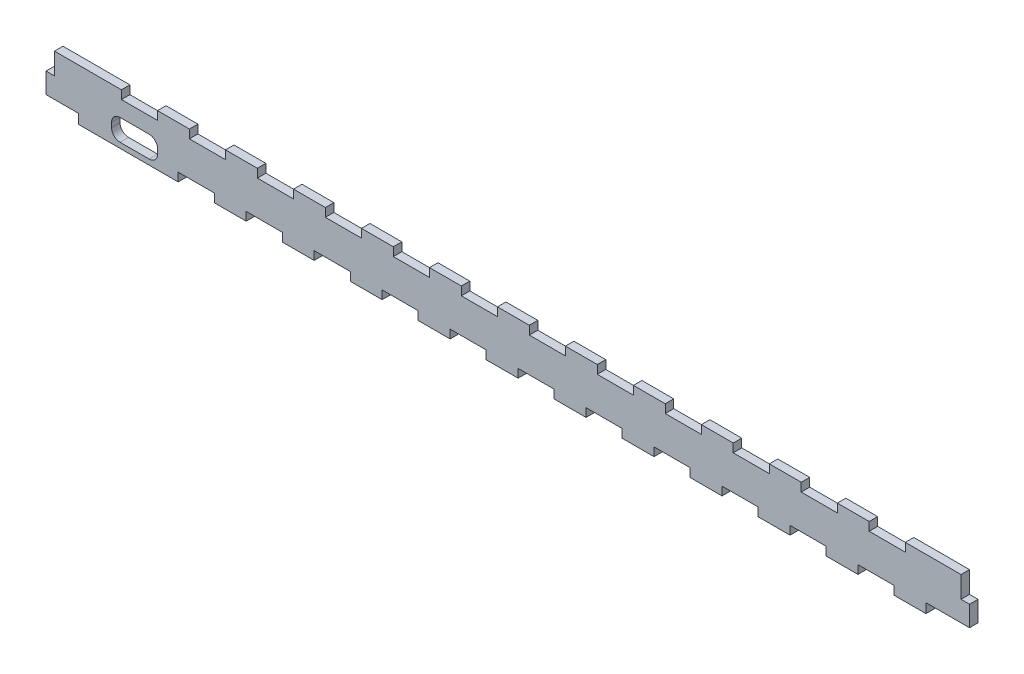
SolidWorks part; units mm, degrees
ref_plane "Plan de face" through (0, 0, 0) normal (0, 0, 1) x (1, 0, 0)
ref_plane "Plan de dessus" through (0, 0, 0) normal (0, 1, 0) x (1, 0, 0)
ref_plane "Plan de droite" through (0, 0, 0) normal (1, 0, 0) x (0, 0, -1)
sketch "Esquisse1" plane through (0, 0, 0) normal (0, 0, 1) x (1, 0, 0)
  line L1 (-108.68, -6.055) -> (108.68, -6.055)
  line L2 (-108.68, -6.055) -> (-108.68, 6.055)
  line L3 (-108.68, 6.055) -> (108.68, 6.055)
  line L4 (108.68, -6.055) -> (108.68, 6.055)
  line L5 (-108.68, -6.055) -> (108.68, 6.055) construction
  line L6 (-108.68, 6.055) -> (108.68, -6.055) construction
  point P0 (0, 0)
extrude "Boss.-Extru.1" add sketch "Esquisse1" along normal blind 2
sketch "Esquisse2" plane through (0, 0, 2) normal (0, 0, 1) x (1, 0, 0)
  line L1 (-109.57, -4.055) -> (-108.68, -4.055)
  line L2 (-109.57, -4.055) -> (-109.57, -6.055)
  line L3 (-109.57, -6.055) -> (-101.07, -6.055)
  line L4 (-101.07, -4.055) -> (-101.07, -6.055)
  line L5 (-90.93, 4.055) -> (-82.43, 4.055)
  line L6 (-90.93, 4.055) -> (-90.93, 6.055)
  line L7 (-90.93, 6.055) -> (-82.43, 6.055)
  line L8 (-82.43, 4.055) -> (-82.43, 6.055)
  line L9 (-108.68, -4.055) -> (-101.32, -4.055) construction
  line L10 (-101.32, -6.055) -> (-108.68, -6.055) construction
  line L12 (-90.68, 4.055) -> (-82.68, 4.055) construction
  line L13 (-90.68, 6.055) -> (-82.68, 6.055) construction
  line L22 (-77.57, -4.055) -> (-69.07, -4.055)
  line L23 (-77.57, -4.055) -> (-77.57, -6.055)
  line L24 (-77.57, -6.055) -> (-69.07, -6.055)
  line L25 (-69.07, -4.055) -> (-69.07, -6.055)
  line L30 (-61.57, -4.055) -> (-53.07, -4.055)
  line L31 (-61.57, -4.055) -> (-61.57, -6.055)
  line L32 (-61.57, -6.055) -> (-53.07, -6.055)
  line L33 (-53.07, -4.055) -> (-53.07, -6.055)
  line L38 (-45.57, -4.055) -> (-37.07, -4.055)
  line L39 (-45.57, -4.055) -> (-45.57, -6.055)
  line L40 (-45.57, -6.055) -> (-37.07, -6.055)
  line L41 (-37.07, -4.055) -> (-37.07, -6.055)
  line L46 (-29.57, -4.055) -> (-21.07, -4.055)
  line L47 (-29.57, -4.055) -> (-29.57, -6.055)
  line L48 (-29.57, -6.055) -> (-21.07, -6.055)
  line L49 (-21.07, -4.055) -> (-21.07, -6.055)
  line L54 (-13.57, -4.055) -> (-5.07, -4.055)
  line L55 (-13.57, -4.055) -> (-13.57, -6.055)
  line L56 (-13.57, -6.055) -> (-5.07, -6.055)
  line L57 (-5.07, -4.055) -> (-5.07, -6.055)
  line L62 (2.43, -4.055) -> (10.93, -4.055)
  line L63 (2.43, -4.055) -> (2.43, -6.055)
  line L64 (2.43, -6.055) -> (10.93, -6.055)
  line L65 (10.93, -4.055) -> (10.93, -6.055)
  line L70 (18.43, -4.055) -> (26.93, -4.055)
  line L71 (18.43, -4.055) -> (18.43, -6.055)
  line L72 (18.43, -6.055) -> (26.93, -6.055)
  line L73 (26.93, -4.055) -> (26.93, -6.055)
  line L78 (34.43, -4.055) -> (42.93, -4.055)
  line L79 (34.43, -4.055) -> (34.43, -6.055)
  line L80 (34.43, -6.055) -> (42.93, -6.055)
  line L81 (42.93, -4.055) -> (42.93, -6.055)
  line L86 (50.43, -4.055) -> (58.93, -4.055)
  line L87 (50.43, -4.055) -> (50.43, -6.055)
  line L88 (50.43, -6.055) -> (58.93, -6.055)
  line L89 (58.93, -4.055) -> (58.93, -6.055)
  line L94 (66.43, -4.055) -> (74.93, -4.055)
  line L95 (66.43, -4.055) -> (66.43, -6.055)
  line L96 (66.43, -6.055) -> (74.93, -6.055)
  line L97 (74.93, -4.055) -> (74.93, -6.055)
  line L102 (82.43, -4.055) -> (90.93, -4.055)
  line L103 (82.43, -4.055) -> (82.43, -6.055)
  line L104 (82.43, -6.055) -> (90.93, -6.055)
  line L105 (90.93, -4.055) -> (90.93, -6.055)
  line L110 (101.07, 4.055) -> (109.57, 4.055) [skipped]
  line L111 (101.07, 4.055) -> (101.07, 6.055) [skipped]
  line L112 (101.07, 6.055) -> (109.57, 6.055) [skipped]
  line L113 (109.57, 4.055) -> (109.57, 6.055) [skipped]
  line L114 (-77.32, -6.055) -> (-77.32, -4.055) construction
  line L115 (-69.32, -4.055) -> (-69.32, -6.055) construction
  line L117 (-74.93, 4.055) -> (-66.43, 4.055) [skipped]
  line L118 (-74.93, 4.055) -> (-74.93, 6.055) [skipped]
  line L119 (-74.93, 6.055) -> (-66.43, 6.055) [skipped]
  line L120 (-66.43, 4.055) -> (-66.43, 6.055) [skipped]
  line L121 (-58.93, 4.055) -> (-50.43, 4.055) [skipped]
  line L122 (-58.93, 4.055) -> (-58.93, 6.055) [skipped]
  line L123 (-58.93, 6.055) -> (-50.43, 6.055) [skipped]
  line L124 (-50.43, 4.055) -> (-50.43, 6.055) [skipped]
  line L125 (-42.93, 4.055) -> (-34.43, 4.055) [skipped]
  line L126 (-42.93, 4.055) -> (-42.93, 6.055) [skipped]
  line L127 (-42.93, 6.055) -> (-34.43, 6.055) [skipped]
  line L128 (-34.43, 4.055) -> (-34.43, 6.055) [skipped]
  line L129 (-26.93, 4.055) -> (-18.43, 4.055) [skipped]
  line L130 (-26.93, 4.055) -> (-26.93, 6.055) [skipped]
  line L131 (-26.93, 6.055) -> (-18.43, 6.055) [skipped]
  line L132 (-18.43, 4.055) -> (-18.43, 6.055) [skipped]
  line L133 (-10.93, 4.055) -> (-2.43, 4.055) [skipped]
  line L134 (-10.93, 4.055) -> (-10.93, 6.055) [skipped]
  line L135 (-10.93, 6.055) -> (-2.43, 6.055) [skipped]
  line L136 (-2.43, 4.055) -> (-2.43, 6.055) [skipped]
  line L137 (5.07, 4.055) -> (13.57, 4.055) [skipped]
  line L138 (5.07, 4.055) -> (5.07, 6.055) [skipped]
  line L139 (5.07, 6.055) -> (13.57, 6.055) [skipped]
  line L140 (13.57, 4.055) -> (13.57, 6.055) [skipped]
  line L141 (21.07, 4.055) -> (29.57, 4.055) [skipped]
  line L142 (21.07, 4.055) -> (21.07, 6.055) [skipped]
  line L143 (21.07, 6.055) -> (29.57, 6.055) [skipped]
  line L144 (29.57, 4.055) -> (29.57, 6.055) [skipped]
  line L145 (37.07, 4.055) -> (45.57, 4.055) [skipped]
  line L146 (37.07, 4.055) -> (37.07, 6.055) [skipped]
  line L147 (37.07, 6.055) -> (45.57, 6.055) [skipped]
  line L148 (45.57, 4.055) -> (45.57, 6.055) [skipped]
  line L149 (53.07, 4.055) -> (61.57, 4.055) [skipped]
  line L150 (53.07, 4.055) -> (53.07, 6.055) [skipped]
  line L151 (53.07, 6.055) -> (61.57, 6.055) [skipped]
  line L152 (61.57, 4.055) -> (61.57, 6.055) [skipped]
  line L153 (69.07, 4.055) -> (77.57, 4.055) [skipped]
  line L154 (69.07, 4.055) -> (69.07, 6.055) [skipped]
  line L155 (69.07, 6.055) -> (77.57, 6.055) [skipped]
  line L156 (77.57, 4.055) -> (77.57, 6.055) [skipped]
  line L157 (85.07, 4.055) -> (93.57, 4.055) [skipped]
  line L158 (85.07, 4.055) -> (85.07, 6.055) [skipped]
  line L159 (85.07, 6.055) -> (93.57, 6.055) [skipped]
  line L160 (93.57, 4.055) -> (93.57, 6.055) [skipped]
  line L161 (-82.68, 4.055) -> (-82.68, 6.055) construction
  line L162 (-74.93, 4.055) -> (-66.43, 4.055)
  line L163 (-74.93, 4.055) -> (-74.93, 6.055)
  line L164 (-74.93, 6.055) -> (-66.43, 6.055)
  line L165 (-66.43, 4.055) -> (-66.43, 6.055)
  line L166 (-58.93, 4.055) -> (-50.43, 4.055)
  line L167 (-58.93, 4.055) -> (-58.93, 6.055)
  line L168 (-58.93, 6.055) -> (-50.43, 6.055)
  line L169 (-50.43, 4.055) -> (-50.43, 6.055)
  line L170 (-42.93, 4.055) -> (-34.43, 4.055)
  line L171 (-42.93, 4.055) -> (-42.93, 6.055)
  line L172 (-42.93, 6.055) -> (-34.43, 6.055)
  line L173 (-34.43, 4.055) -> (-34.43, 6.055)
  line L174 (-26.93, 4.055) -> (-18.43, 4.055)
  line L175 (-26.93, 4.055) -> (-26.93, 6.055)
  line L176 (-26.93, 6.055) -> (-18.43, 6.055)
  line L177 (-18.43, 4.055) -> (-18.43, 6.055)
  line L178 (-10.93, 4.055) -> (-2.43, 4.055)
  line L179 (-10.93, 4.055) -> (-10.93, 6.055)
  line L180 (-10.93, 6.055) -> (-2.43, 6.055)
  line L181 (-2.43, 4.055) -> (-2.43, 6.055)
  line L182 (5.07, 4.055) -> (13.57, 4.055)
  line L183 (5.07, 4.055) -> (5.07, 6.055)
  line L184 (5.07, 6.055) -> (13.57, 6.055)
  line L185 (13.57, 4.055) -> (13.57, 6.055)
  line L186 (21.07, 4.055) -> (29.57, 4.055)
  line L187 (21.07, 4.055) -> (21.07, 6.055)
  line L188 (21.07, 6.055) -> (29.57, 6.055)
  line L189 (29.57, 4.055) -> (29.57, 6.055)
  line L190 (37.07, 4.055) -> (45.57, 4.055)
  line L191 (37.07, 4.055) -> (37.07, 6.055)
  line L192 (37.07, 6.055) -> (45.57, 6.055)
  line L193 (45.57, 4.055) -> (45.57, 6.055)
  line L194 (53.07, 4.055) -> (61.57, 4.055)
  line L195 (53.07, 4.055) -> (53.07, 6.055)
  line L196 (53.07, 6.055) -> (61.57, 6.055)
  line L197 (61.57, 4.055) -> (61.57, 6.055)
  line L198 (69.07, 4.055) -> (77.57, 4.055)
  line L199 (69.07, 4.055) -> (69.07, 6.055)
  line L200 (69.07, 6.055) -> (77.57, 6.055)
  line L201 (77.57, 4.055) -> (77.57, 6.055)
  line L202 (85.07, 4.055) -> (93.57, 4.055)
  line L203 (85.07, 4.055) -> (85.07, 6.055)
  line L204 (85.07, 6.055) -> (93.57, 6.055)
  line L205 (93.57, 4.055) -> (93.57, 6.055)
  line L206 (93.32, 4.055) -> (93.32, 6.055) construction
  line L207 (90.68, -4.055) -> (90.68, -6.055) construction
  line L208 (82.68, -4.055) -> (90.68, -4.055) construction
  line L209 (-108.68, -6.055) -> (108.68, -6.055) construction
  line L210 (98.43, -6.055) -> (108.68, -6.055)
  line L211 (98.43, -6.055) -> (98.43, -3.805)
  line L212 (98.43, -3.805) -> (108.68, -3.805)
  line L213 (108.68, -6.055) -> (108.68, -3.805)
  line L214 (108.68, -6.055) -> (108.68, 6.055) construction
  line L215 (108.68, -4.055) -> (98.68, -4.055) construction
  line L216 (98.68, -6.055) -> (98.68, -4.055) construction
  line L218 (-108.68, -4.055) -> (-101.07, -4.055) construction
  line L219 (-108.68, -4.055) -> (-108.68, -3.805)
  line L220 (-108.68, -3.805) -> (-101.07, -3.805)
  line L221 (-101.07, -4.055) -> (-101.07, -3.805)
  line L223 (-108.68, -4.055) -> (-101.07, -4.055) construction
  line L224 (-93.57, -4.055) -> (-85.07, -4.055) [skipped]
  line L225 (-93.57, -4.055) -> (-93.57, -6.055) [skipped]
  line L226 (-93.57, -6.055) -> (-85.07, -6.055) [skipped]
  line L227 (-85.07, -4.055) -> (-85.07, -6.055) [skipped]
  point P3 (-89, -4.055)
  point P8 (-105, -4.055)
  point P17 (-86.68, 4.055)
  point P24 (105.32, 4.055)
  point P28 (89.32, 4.055)
  point P29 (73.32, 4.055)
  point P30 (57.32, 4.055)
  point P31 (41.32, 4.055)
  point P38 (25.32, 4.055)
  point P39 (9.32, 4.055)
  point P40 (-6.68, 4.055)
  point P41 (-22.68, 4.055)
  point P42 (-73, -4.055)
  point P43 (-70.68, 4.055)
  point P48 (-38.68, 4.055)
  point P49 (-54.68, 4.055)
  point P52 (-57, -4.055)
  point P58 (-70.68, 4.055)
  point P62 (-41, -4.055)
  point P68 (-54.68, 4.055)
  point P72 (-25, -4.055)
  point P78 (-38.68, 4.055)
  point P82 (-9, -4.055)
  point P88 (-22.68, 4.055)
  point P92 (7, -4.055)
  point P98 (-6.68, 4.055)
  point P102 (23, -4.055)
  point P108 (9.32, 4.055)
  point P112 (39, -4.055)
  point P118 (25.32, 4.055)
  point P122 (55, -4.055)
  point P128 (41.32, 4.055)
  point P132 (71, -4.055)
  point P141 (57.32, 4.055)
  point P142 (87, -4.055)
  point P243 (73.32, 4.055)
  point P248 (89.32, 4.055)
  dimension "D1" = 0.25
  dimension "D2" = 0.25
  dimension "D4" = 0.25
  dimension "D6" = 0.25
  dimension "D7" = 0.25
  dimension "D8" = 0.25
  dimension "D9" = 0.25
  dimension "D10" = 0.25
  dimension "D3" = 13
  dimension "D5" = 12
extrude "Enlèv. mat.-Extru.1" cut sketch "Esquisse2" against normal through all
sketch "Esquisse3" plane through (0, 0, 2) normal (0, 0, 1) x (1, 0, 0)
  line L0 (-93.002, -1.925) -> (-93.002, -2.625) construction
  line L1 (-91.252, 0.255) -> (-84.412, 0.255)
  line L2 (-93.252, -1.745) -> (-93.252, -2.805)
  line L3 (-91.252, -4.805) -> (-84.412, -4.805)
  line L4 (-82.412, -1.745) -> (-82.412, -2.805)
  line L5 (-82.662, -2.625) -> (-82.662, -1.925) construction
  line L6 (-84.592, 0.005) -> (-91.072, 0.005) construction
  line L7 (-91.072, -4.555) -> (-84.592, -4.555) construction
  arc A0 (-93.252, -2.805) -> (-91.252, -4.805) centre (-91.252, -2.805) ccw
  arc A1 (-84.412, 0.255) -> (-82.412, -1.745) centre (-84.412, -1.745) cw
  arc A2 (-84.412, -4.805) -> (-82.412, -2.805) centre (-84.412, -2.805) ccw
  arc A3 (-91.252, 0.255) -> (-93.252, -1.745) centre (-91.252, -1.745) ccw
  dimension "D5" = 2
  dimension "D1" = 0.25
  dimension "D2" = 0.25
  dimension "D3" = 0.25
  dimension "D4" = 0.25
extrude "Enlèv. mat.-Extru.2" cut sketch "Esquisse3" against normal through all
sketch "Esquisse5" plane through (0, 0, 2) normal (0, 0, 1) x (1, 0, 0)
  line L0 (0, 0) -> (0, -11.5957) construction
  line L1 (-108.68, 1) -> (-106.68, 1)
  line L2 (-108.68, 1) -> (-108.68, 6.055)
  line L3 (-108.68, 6.055) -> (-106.68, 6.055)
  line L4 (-106.68, 1) -> (-106.68, 6.055)
  line L5 (106.68, 1) -> (106.68, 6.055)
  line L6 (108.68, 6.055) -> (106.68, 6.055)
  line L7 (108.68, 1) -> (108.68, 6.055)
  line L8 (108.68, 1) -> (106.68, 1)
extrude "Enlèv. mat.-Extru.3" cut sketch "Esquisse5" against normal through all
